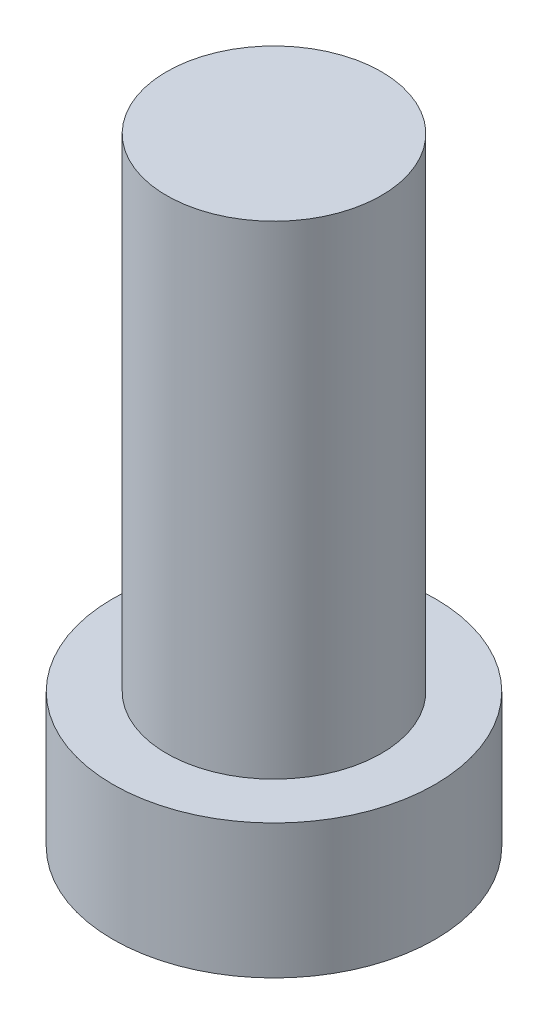
SolidWorks part; units mm, degrees
ref_plane "Front Plane" through (0, 0, 0) normal (0, 0, 1) x (1, 0, 0)
ref_plane "Top Plane" through (0, 0, 0) normal (0, 1, 0) x (1, 0, 0)
ref_plane "Right Plane" through (0, 0, 0) normal (1, 0, 0) x (0, 0, -1)
sketch "Sketch1" plane through (0, 0, 0) normal (0, 1, 0) x (1, 0, 0)
  circle A0 centre (0, 0) radius 30
  dimension "D1" = 60
extrude "Boss-Extrude1" add sketch "Sketch1" along normal blind 25
sketch "Sketch2" plane through (0, 25, 0) normal (0, 1, 0) x (1, 0, 0)
  circle A0 centre (0, 0) radius 20
  dimension "D1" = 40
extrude "Boss-Extrude2" add sketch "Sketch2" along normal blind 90
ref_axis "Axis1" through (0, 115, 0) along (0, -1, 0)
